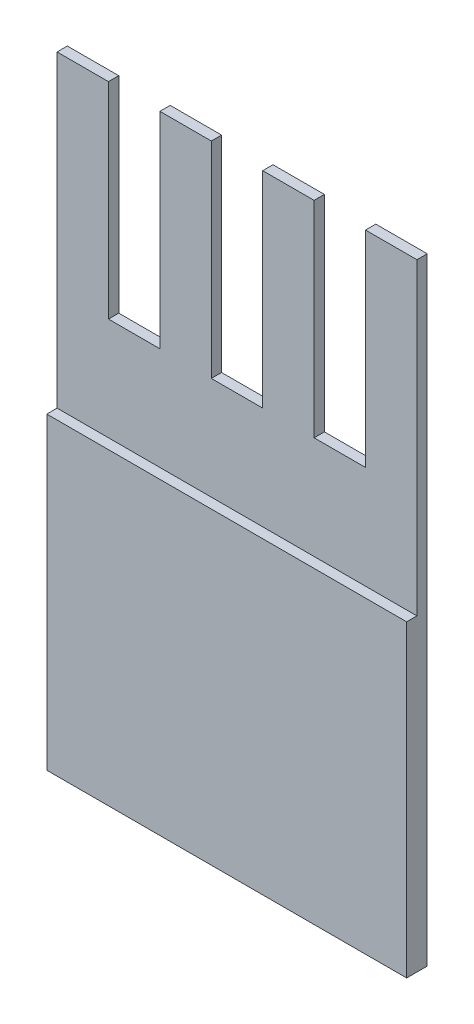
SolidWorks part; units mm, degrees
ref_plane "Front" through (0, 0, 0) normal (0, 0, 1) x (1, 0, 0)
ref_plane "Top" through (0, 0, 0) normal (0, 1, 0) x (1, 0, 0)
ref_plane "Side" through (0, 0, 0) normal (1, 0, 0) x (0, 0, -1)
sketch "Sketch1" plane through (0, 0, 0) normal (0, 0, 1) x (1, 0, 0)
  line L0 (-12.5, 30) -> (-17.5, 30)
  line L1 (17.5, 30) -> (12.5, 30)
  line L2 (17.5, 30) -> (17.5, -30)
  line L3 (17.5, -30) -> (-17.5, -30)
  line L4 (-17.5, 30) -> (-17.5, -30)
  line L5 (-2.5, 10) -> (2.5, 10)
  line L6 (-12.5, 10) -> (-7.5, 10)
  line L7 (-17.5, 30) -> (-12.5, 30)
  line L8 (-17.5, 30) -> (-17.5, 10)
  line L9 (-12.5, 10) -> (-7.5, 10)
  line L10 (17.5, 30) -> (17.5, 10)
  line L20 (-2.5, 30) -> (-2.5, 10)
  line L21 (-2.5, 10) -> (2.5, 10)
  line L22 (2.5, 30) -> (2.5, 10)
  line L24 (-7.5, 30) -> (-7.5, 10)
  line L25 (-7.5, 10) -> (-12.5, 10)
  line L26 (-12.5, 30) -> (-12.5, 10)
  line L28 (7.5, 30) -> (7.5, 10)
  line L29 (7.5, 10) -> (12.5, 10)
  line L30 (12.5, 30) -> (12.5, 10)
  line L31 (-7.5, 30) -> (-2.5, 30)
  line L32 (-17.5, 10) -> (-17.5, 0)
  line L33 (-2.5, 30) -> (-7.5, 30)
  line L34 (2.5, 30) -> (7.5, 30)
  line L35 (7.5, 30) -> (2.5, 30)
  line L36 (12.5, 30) -> (17.5, 30)
  line L37 (-17.5, 0) -> (17.5, 0)
  line L38 (17.5, 10) -> (17.5, 0)
  line L39 (-2.5, 10) -> (2.5, 10)
  line L40 (7.5, 10) -> (12.5, 10)
  line L41 (7.5, 10) -> (12.5, 10)
  point P0 (0, 0)
extrude "Boss-Extrude5" add sketch "Sketch1" along normal blind 2 contours L37 L4 L3 L2 region at (0, -15, 0)
extrude "Boss-Extrude6" add sketch "Sketch1<7>" along normal blind 1 contours L4 L37 L2 L1 L30 L29 L28 L34 L22 L5 L20 L31 L24 L6 L26 L0 region at (-12.961, 20, 0)
sketch "Sketch1<7>" plane through (0, 0, 0) normal (0, 0, 1) x (1, 0, 0) same geometry as "Sketch1"
